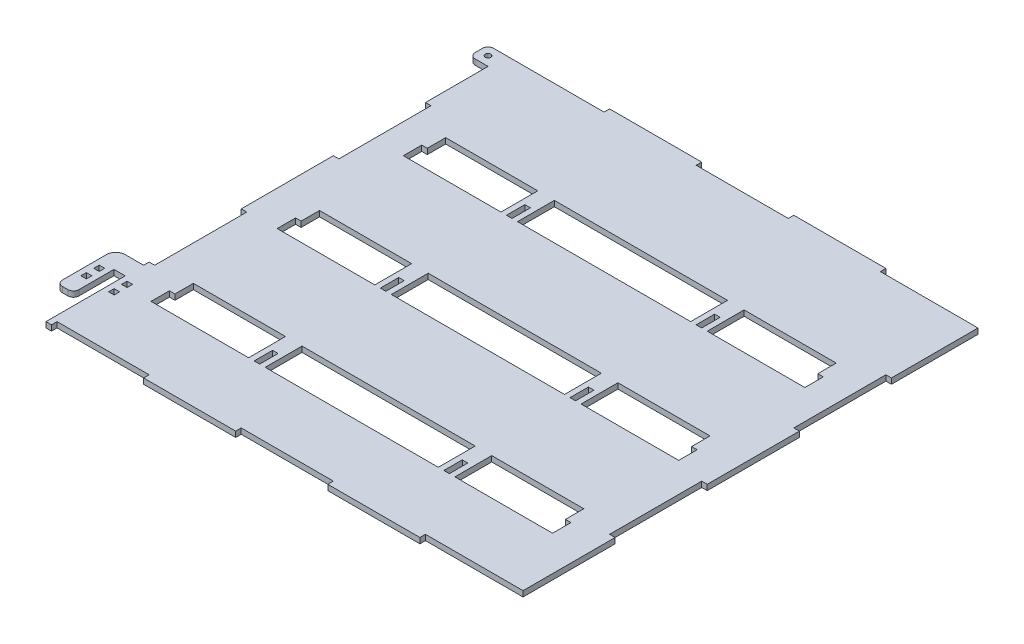
SolidWorks part; units mm, degrees
ref_plane "Front Plane" through (0, 0, 0) normal (0, 0, 1) x (1, 0, 0)
ref_plane "Top Plane" through (0, 0, 0) normal (0, 1, 0) x (1, 0, 0)
ref_plane "Right Plane" through (0, 0, 0) normal (1, 0, 0) x (0, 0, -1)
sketch "Sketch1" plane through (0, 0, 0) normal (0, 1, 0) x (1, 0, 0)
  line L0 (256, 100) -> (256, 150)
  line L1 (3, 0) -> (53, 0)
  line L2 (0, 0) -> (0, 40)
  line L3 (53, 250) -> (103, 250)
  line L4 (256, 0) -> (256, 50)
  line L5 (0, 203) -> (0, 237)
  line L6 (203, 250) -> (153, 250)
  line L7 (0, 50) -> (-10.1, 50)
  line L8 (0, 0) -> (0, -3)
  line L9 (256, 200) -> (253, 200)
  line L10 (0, -3) -> (3, -3)
  line L11 (256, 150) -> (253, 150)
  line L12 (253, 200) -> (253, 150)
  line L13 (203, 0) -> (256, 0)
  line L14 (153, 0) -> (153, -3)
  line L15 (153, -3) -> (203, -3)
  line L16 (203, 0) -> (203, -3)
  line L17 (0, 203) -> (3, 203)
  line L18 (0, 103) -> (0, 153)
  line L19 (0, 153) -> (3, 153)
  line L20 (3, 203) -> (3, 153)
  line L21 (3, 0) -> (3, -3)
  line L22 (103, 0) -> (103, -3)
  line L23 (103, -3) -> (53, -3)
  line L24 (53, 0) -> (53, -3)
  line L25 (-12.1, 28) -> (-9.1, 28)
  line L26 (0, 40) -> (-6.1, 40)
  line L27 (-15.1, 45) -> (-15.1, 43)
  line L28 (-12.1, 28) -> (-12.1, 31)
  line L29 (256, 100) -> (253, 100)
  line L30 (256, 200) -> (256, 247)
  line L31 (256, 50) -> (253, 50)
  line L32 (253, 100) -> (253, 50)
  line L33 (0, 103) -> (3, 103)
  line L34 (103, 0) -> (153, 0)
  line L35 (-7, 247) -> (53, 247)
  line L36 (3, 103) -> (3, 53)
  line L37 (184, 172) -> (234, 172)
  line L38 (-15.1, 43) -> (-15.1, 21)
  line L39 (0, 237) -> (-7, 237)
  line L40 (-10, 244) -> (-10, 240)
  line L41 (-12.1, 18) -> (-9.1, 18)
  line L42 (-6.1, 40) -> (-6.1, 21)
  line L43 (-12.1, 31) -> (-9.1, 31)
  line L44 (-9.1, 28) -> (-9.1, 31)
  line L45 (-12.1, 35) -> (-9.1, 35)
  line L46 (-12.1, 35) -> (-12.1, 38)
  line L47 (-12.1, 38) -> (-9.1, 38)
  line L48 (-9.1, 35) -> (-9.1, 38)
  line L49 (3, 28) -> (6, 28)
  line L50 (3, 28) -> (3, 31)
  line L51 (3, 31) -> (6, 31)
  line L52 (6, 28) -> (6, 31)
  line L53 (3, 35) -> (6, 35)
  line L54 (3, 35) -> (3, 38)
  line L55 (3, 38) -> (6, 38)
  line L56 (6, 35) -> (6, 38)
  line L57 (75, 35) -> (78, 35)
  line L58 (75, 35) -> (75, 45)
  line L59 (203, 250) -> (203, 247)
  line L60 (203, 247) -> (256, 247)
  line L61 (0, 50) -> (0, 53)
  line L62 (103, 250) -> (103, 247)
  line L63 (103, 247) -> (153, 247)
  line L64 (153, 250) -> (153, 247)
  line L65 (0, 53) -> (3, 53)
  line L66 (75, 45) -> (78, 45)
  line L67 (78, 35) -> (78, 45)
  line L68 (53, 250) -> (53, 247)
  line L69 (178, 35) -> (181, 35)
  line L70 (178, 35) -> (178, 45)
  line L71 (178, 45) -> (181, 45)
  line L72 (181, 35) -> (181, 45)
  line L73 (75, 103.5) -> (78, 103.5)
  line L74 (75, 103.5) -> (75, 113.5)
  line L75 (75, 113.5) -> (78, 113.5)
  line L76 (78, 103.5) -> (78, 113.5)
  line L77 (22, 172) -> (72, 172)
  line L78 (181, 103.5) -> (181, 113.5)
  line L79 (181, 113.5) -> (178, 113.5)
  line L80 (178, 103.5) -> (178, 113.5)
  line L81 (81, 123.5) -> (175, 123.5)
  line L82 (75, 172) -> (75, 182)
  line L83 (75, 182) -> (78, 182)
  line L84 (78, 172) -> (78, 182)
  line L85 (184, 123.5) -> (234, 123.5)
  line L86 (178, 172) -> (178, 182)
  line L87 (178, 182) -> (181, 182)
  line L88 (181, 172) -> (181, 182)
  line L89 (22, 35) -> (72, 35)
  line L90 (22, 45) -> (22, 55)
  line L91 (22, 55) -> (72, 55)
  line L92 (234, 45) -> (234, 55)
  line L93 (22, 103.5) -> (72, 103.5)
  line L94 (72, 35) -> (72, 55)
  line L95 (81, 192) -> (175, 192)
  line L96 (81, 35) -> (81, 55)
  line L97 (22, 113.5) -> (22, 123.5)
  line L98 (175, 35) -> (175, 55)
  line L99 (81, 55) -> (175, 55)
  line L100 (184, 35) -> (184, 55)
  line L101 (81, 35) -> (175, 35)
  line L102 (22, 123.5) -> (72, 123.5)
  line L103 (184, 35) -> (234, 35)
  line L104 (234, 113.5) -> (234, 123.5)
  line L105 (22, 182) -> (22, 192)
  line L106 (72, 103.5) -> (72, 123.5)
  line L107 (184, 55) -> (234, 55)
  line L108 (81, 103.5) -> (81, 123.5)
  line L109 (22, 192) -> (72, 192)
  line L110 (175, 103.5) -> (175, 123.5)
  line L111 (184, 192) -> (234, 192)
  line L112 (184, 103.5) -> (184, 123.5)
  line L113 (81, 103.5) -> (175, 103.5)
  line L114 (181, 103.5) -> (178, 103.5)
  line L115 (184, 103.5) -> (234, 103.5)
  line L116 (234, 182) -> (234, 192)
  line L117 (75, 172) -> (78, 172)
  line L118 (72, 172) -> (72, 192)
  line L120 (81, 172) -> (81, 192)
  line L121 (178, 172) -> (181, 172)
  line L122 (175, 172) -> (175, 192)
  line L123 (234, 35) -> (237, 35)
  line L124 (184, 172) -> (184, 192)
  line L125 (81, 172) -> (175, 172)
  line L127 (234, 45) -> (237, 45)
  line L128 (237, 35) -> (237, 45)
  line L129 (22, 35) -> (19, 35)
  line L131 (22, 45) -> (19, 45)
  line L132 (19, 35) -> (19, 45)
  line L133 (22, 103.5) -> (19, 103.5)
  line L135 (22, 113.5) -> (19, 113.5)
  line L136 (19, 103.5) -> (19, 113.5)
  line L137 (22, 172) -> (19, 172)
  line L139 (22, 182) -> (19, 182)
  line L140 (19, 172) -> (19, 182)
  line L141 (234, 172) -> (237, 172)
  line L143 (234, 182) -> (237, 182)
  line L144 (237, 172) -> (237, 182)
  line L145 (234, 103.5) -> (237, 103.5)
  line L147 (234, 113.5) -> (237, 113.5)
  line L148 (237, 103.5) -> (237, 113.5)
  circle A0 centre (-5, 242) radius 1.5
  arc A1 (-7, 247) -> (-10, 244) centre (-7, 244) ccw
  arc A2 (-7, 237) -> (-10, 240) centre (-7, 240) cw
  arc A3 (-10.1, 50) -> (-15.1, 45) centre (-10.1, 45) ccw
  arc A4 (-9.1, 18) -> (-6.1, 21) centre (-9.1, 21) ccw
  arc A5 (-15.1, 21) -> (-12.1, 18) centre (-12.1, 21) ccw
  point P45 (-10, 247)
  point P48 (-10, 237)
  point P67 (-15.1, 50)
  point P70 (-6.1, 18)
  point P73 (-15.1, 18)
  dimension "D7" = 5
  dimension "D8" = 3
  dimension "D9" = 5
  dimension "D10" = 3
  dimension "D45" = 5
  dimension "D46" = 3
  dimension "D12" = 3
  dimension "D84" = 3
  dimension "D1" = 256
  dimension "D3" = 50
  dimension "D4" = 3
  dimension "D5" = 10
  dimension "D6" = 10
  dimension "D11" = 34
  dimension "D13" = 53
  dimension "D14" = 3
  dimension "D15" = 3
  dimension "D16" = 50
  dimension "D17" = 50
  dimension "D18" = 50
  dimension "D19" = 53
  dimension "D20" = 3
  dimension "D21" = 3
  dimension "D22" = 50
  dimension "D23" = 50
  dimension "D24" = 50
  dimension "D25" = 50
  dimension "D26" = 50
  dimension "D27" = 3
  dimension "D28" = 3
  dimension "D29" = 50
  dimension "D30" = 50
  dimension "D31" = 9
  dimension "D32" = 15.1
  dimension "D33" = 25
  dimension "D34" = 7
  dimension "D35" = 40
  dimension "D36" = 4
  dimension "D37" = 4
  dimension "D38" = 10
  dimension "D39" = 3
  dimension "D40" = 10
  dimension "D41" = 3
  dimension "D42" = 3
  dimension "D43" = 3
  dimension "D44" = 3
  dimension "D47" = 6.1
  dimension "D48" = 50
  dimension "D49" = 50
  dimension "D50" = 50
  dimension "D51" = 53
  dimension "D52" = 247
  dimension "D53" = 47
  dimension "D54" = 3
  dimension "D55" = 50
  dimension "D56" = 3
  dimension "D57" = 10
  dimension "D58" = 65
  dimension "D59" = 20
  dimension "D60" = 10
  dimension "D61" = 100
  dimension "D62" = 3
  dimension "D63" = 75
  dimension "D64" = 3
  dimension "D65" = 65
  dimension "D66" = 20
  dimension "D67" = 3
  dimension "D68" = 3
  dimension "D69" = 58.5
  dimension "D70" = 10
  dimension "D71" = 90
  dimension "D72" = 3
  dimension "D73" = 10
  dimension "D74" = 20
  dimension "D75" = 3
  dimension "D76" = 3
  dimension "D77" = 3
  dimension "D78" = 50
  dimension "D79" = 50
  dimension "D80" = 20
  dimension "D81" = 20
  dimension "D82" = 58.5
  dimension "D83" = 90
  dimension "D85" = 3
  dimension "D86" = 3
  dimension "D87" = 5
  dimension "D88" = 5
  dimension "D89" = 10
  dimension "D90" = 100
  dimension "D91" = 75
  dimension "D92" = 3
  dimension "D93" = 20
  dimension "D94" = 3
  dimension "D95" = 20
  dimension "D96" = 20
  dimension "D97" = 90
  dimension "D98" = 90
  dimension "D99" = 3
  dimension "D100" = 10
  dimension "D101" = 20
  dimension "D102" = 6
  dimension "D103" = 6
  dimension "D104" = 58.5
  dimension "D105" = 75
  dimension "D106" = 50
  dimension "D107" = 50
  dimension "D108" = 103
  dimension "D109" = 10
  dimension "D110" = 10
  dimension "D111" = 3
  dimension "D112" = 3
  dimension "D113" = 3
  dimension "D114" = 50
  dimension "D115" = 3
  dimension "D116" = 3
  dimension "D117" = 10
  dimension "D118" = 20
  dimension "D119" = 20
  dimension "D120" = 50
  dimension "D121" = 50
  dimension "D122" = 58.5
  dimension "D123" = 10
  dimension "D124" = 50
  dimension "D125" = 94
  dimension "D126" = 94
extrude "Boss-Extrude1" add sketch "Sketch1" along normal blind 3
equation "\"w\"=3"
equation "\"L\"=50"
